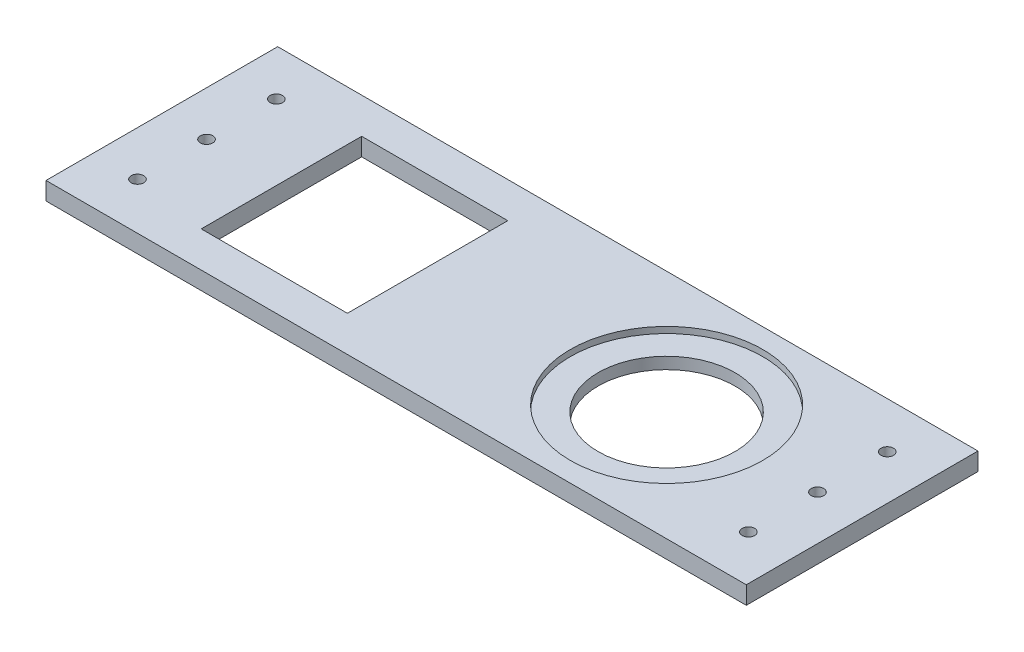
SolidWorks part; units mm, degrees
ref_plane "Front Plane" through (0, 0, 0) normal (0, 0, 1) x (1, 0, 0)
ref_plane "Top Plane" through (0, 0, 0) normal (0, 1, 0) x (1, 0, 0)
ref_plane "Right Plane" through (0, 0, 0) normal (1, 0, 0) x (0, 0, -1)
sketch "Sketch2" plane through (0, 0, 0) normal (0, 1, 0) x (1, 0, 0)
  line L1 (96.45, 76.7) -> (-100, 76.7)
  line L2 (96.45, 76.7) -> (96.45, -75)
  line L3 (96.45, -75) -> (-100, -75)
  line L4 (-100, 76.7) -> (-100, -75)
  line L5 (96.45, 76.7) -> (-100, -75) construction
  line L6 (96.45, -75) -> (-100, 76.7) construction
  point P0 (-1.775, 0.85)
  dimension "D1" = 151.7
  dimension "D2" = 196.45
extrude "Boss-Extrude1" add sketch "Sketch2" along normal blind 5 contours L4 L3 L2 L1
sketch "Sketch3" plane through (0, 0, 0) normal (0, 1, 0) x (1, 0, 0)
  line L0 (0, 0) -> (22.385, 0) construction
  line L1 (0, 0) -> (-25.4527, 0) construction
  line L6 (-66.4527, -22.5) -> (-25.4527, -22.5)
  line L7 (-66.4527, -22.5) -> (-66.4527, 22.5)
  line L8 (-25.4527, -22.5) -> (-25.4527, 22.5)
  line L9 (-66.4527, 22.5) -> (-25.4527, 22.5)
  line L10 (-66.4527, -22.5) -> (-25.4527, 22.5) construction
  line L11 (-25.4527, -22.5) -> (-66.4527, 22.5) construction
  circle A1 centre (41.585, 0) radius 19.2
  point P7 (-45.9527, 0)
  dimension "D1" = 38.4
  dimension "D2" = 41
  dimension "D4" = 25.4527
  dimension "D3" = 45
  dimension "D5" = 22.385
extrude "Cut-Extrude2" cut sketch "Sketch3" against normal blind 22 and the other way blind 15
sketch "Sketch4" plane through (0, 5, 0) normal (0, 1, 0) x (1, 0, 0)
  circle A0 centre (41.585, 0) radius 26.99
  dimension "D1" = 53.98
extrude "Cut-Extrude3" cut sketch "Sketch4" against normal blind 1.74
ref_plane "Plane1" through (-15.4527, 0, -32.5) normal (-1, 0, 0) x (0, 0, 1)
sketch "Sketch9" plane through (0, 5, 0) normal (0, 1, 0) x (1, 0, 0)
  line L0 (72.8814, 32.5) -> (96.45, 32.5)
  line L1 (-76.4527, 32.5) -> (72.8814, 32.5)
  line L3 (-76.4527, -32.5) -> (72.8814, -32.5)
  line L13 (96.45, 32.5) -> (96.45, -32.5)
  line L15 (-76.4527, 32.5) -> (-100, 32.5)
  line L16 (-100, 76.7) -> (-100, -75) construction
  line L17 (-100, 32.5) -> (-100, -32.5)
  line L18 (-100, -32.5) -> (-76.4527, -32.5)
  line L19 (72.8814, -32.5) -> (96.45, -32.5)
  line M10 (96.45, 76.7) -> (-100, 76.7)
  line M11 (-100, 76.7) -> (-100, -75)
  line M12 (-100, -75) -> (96.45, -75)
  line M13 (96.45, -75) -> (96.45, 76.7)
extrude "Cut-Extrude7" cut sketch "Sketch9" against normal blind 20 contours L1 L3 M10 M13 | M11 M12 region at (-1.775, 5, -54.6) region at (-1.775, 5, 53.75)
sketch "Sketch10" plane through (-19.6227, -51.7665, -93.2799) normal (0, 1, 0) x (1, 0, 0)
  circle A0 centre (-67.8448, -93.2799) radius 1.75
  circle A1 centre (-67.8448, -112.6473) radius 1.75
  circle A2 centre (-67.8448, -73.6962) radius 1.75
  circle A3 centre (103.5402, -73.6962) radius 1.75
  circle A4 centre (103.5402, -93.2799) radius 1.75
  circle A5 centre (103.5402, -112.6473) radius 1.75
  point P12 (0, 0)
extrude "Cut-Extrude8" cut sketch "Sketch10" along normal blind 71
